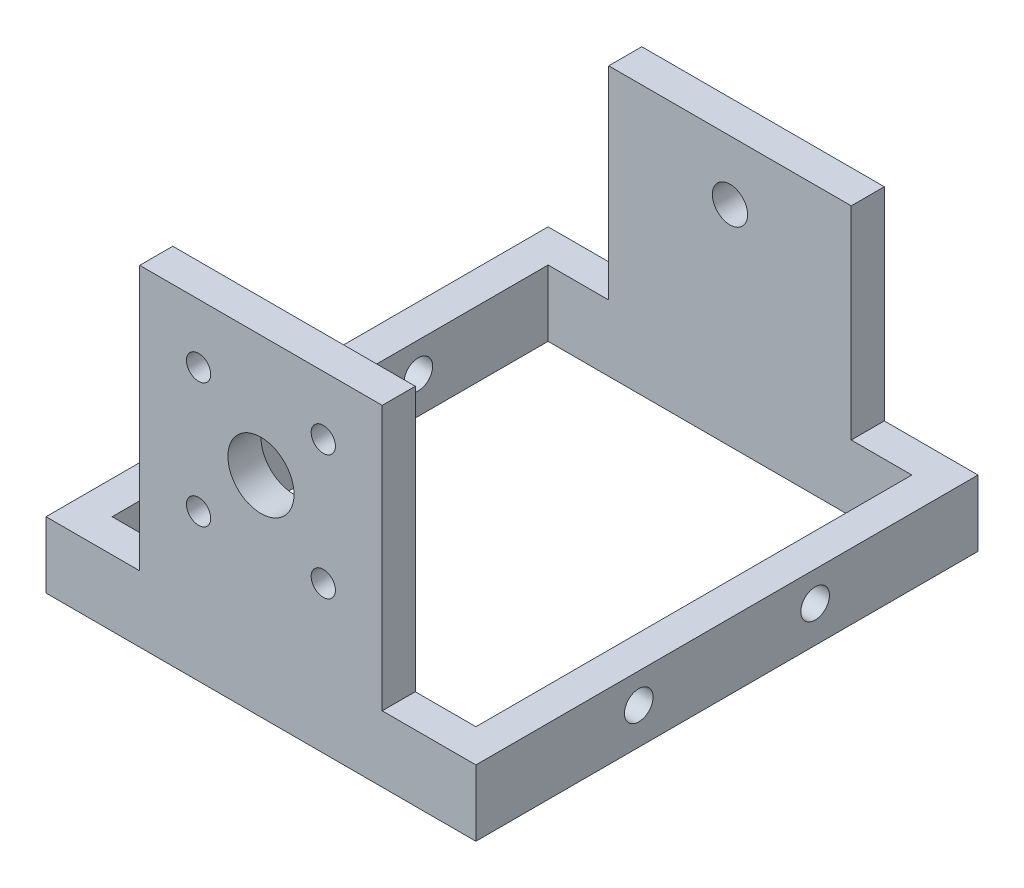
SolidWorks part; units mm, degrees
ref_plane "Front Plane" through (0, 0, 0) normal (0, 0, 1) x (1, 0, 0)
ref_plane "Top Plane" through (0, 0, 0) normal (0, 1, 0) x (1, 0, 0)
ref_plane "Right Plane" through (0, 0, 0) normal (1, 0, 0) x (0, 0, -1)
sketch "Sketch1" plane through (0, 0, 0) normal (0, 1, 0) x (1, 0, 0)
  line L0 (-55, 0) -> (55, 0) construction
  line L1 (19.5, 22.775) -> (-19.5, 22.775)
  line L2 (19.5, 22.775) -> (19.5, -22.775)
  line L3 (19.5, -22.775) -> (-19.5, -22.775)
  line L4 (-19.5, 22.775) -> (-19.5, -22.775)
  line L5 (19.5, 22.775) -> (-19.5, -22.775) construction
  line L6 (19.5, -22.775) -> (-19.5, 22.775) construction
  line L7 (16.5, 19.775) -> (-16.5, 19.775)
  line L8 (16.5, 19.775) -> (16.5, -19.775)
  line L9 (16.5, -19.775) -> (-16.5, -19.775)
  line L10 (-16.5, 19.775) -> (-16.5, -19.775)
  line L11 (16.5, 19.775) -> (-16.5, -19.775) construction
  line L12 (16.5, -19.775) -> (-16.5, 19.775) construction
  line L13 (-11, -19.775) -> (11, -19.775)
  line L14 (-11, -19.775) -> (-11, -22.775)
  line L15 (-11, -22.775) -> (11, -22.775)
  line L16 (11, -19.775) -> (11, -22.775)
  line L17 (-11, 22.775) -> (11, 22.775)
  line L18 (11, 19.775) -> (11, 22.775)
  line L19 (-11, 19.775) -> (11, 19.775)
  line L20 (-11, 19.775) -> (-11, 22.775)
  point P0 (0, 0)
  point P6 (0, 0)
  point P15 (0, -19.775)
  dimension "D1" = 33
  dimension "D2" = 3
  dimension "D3" = 3
  dimension "D4" = 39.55
  dimension "D5" = 22
extrude "Boss-Extrude1" add sketch "Sketch1" along normal blind 6 contours L7 L20 L1 L4 L3 L14 L9 L10 | L18 L7 L8 L9 L16 L3 L2 L1 region at (17.1733, 0, 0) region at (-17.1733, 0, 0)
extrude "Boss-Extrude2" add sketch "Sketch1<3>" along normal blind 30 contours L16 L9 L14 L3 region at (0, 0, 21.275)
sketch "Sketch1<3>" plane through (0, 0, 0) normal (0, 1, 0) x (1, 0, 0) same geometry as "Sketch1"
extrude "Boss-Extrude3" add sketch "Sketch1<4>" along normal blind 24.4 contours L20 L7 L18 L1 region at (0, 0, -21.275)
sketch "Sketch1<4>" plane through (0, 0, 0) normal (0, 1, 0) x (1, 0, 0) same geometry as "Sketch1"
sketch "Sketch3" plane through (-19.5, 0, 0) normal (-1, 0, 0) x (0, 0, 1)
  line L1 (0, -16.5) -> (0, 16.5) construction
  line L2 (21.45, 0) -> (-21.45, 0) construction
  circle A0 centre (-8, 3.3) radius 1.3
  circle A1 centre (8, 3.3) radius 1.3
  dimension "D1" = 2.6
  dimension "D2" = 8
  dimension "D3" = 3.3
extrude "Cut-Extrude1" cut sketch "Sketch3" against normal up to surface (39 mm away) up to face at (19.5, 3, 0)
sketch "Sketch4" plane through (0, 0, -22.775) normal (0, 0, -1) x (-1, 0, 0)
  line L0 (-11, 24.4) -> (11, 24.4) construction
  circle A0 centre (0, 19) radius 1.6
  point P4 (0, 24.4)
  dimension "D2" = 3.2
  dimension "D1" = 5.4
extrude "Cut-Extrude2" cut sketch "Sketch4" against normal up to surface (3 mm away) up to face at (0, 9.1, -19.775)
sketch "Sketch5" plane through (0, 0, 22.775) normal (0, 0, 1) x (1, 0, 0)
  line L0 (-11, 30) -> (11, 8) construction
  line L1 (11, 30) -> (11, 6) construction
  line L2 (11, 30) -> (-11, 8) construction
  line L3 (-11, 30) -> (-11, 6) construction
  circle A0 centre (0, 19) radius 3
  circle A1 centre (5.6569, 24.6569) radius 1.1
  dimension "D2" = 6
  dimension "D3" = 2.2
  dimension "D1" = 22
  dimension "D4" = 8
extrude "Cut-Extrude3" cut sketch "Sketch5" against normal up to surface (3 mm away) up to face at (0, 10.5, 19.775)
pattern_circular "CirPattern1" count 4 over 360 about axis through (0, 19, 22.775) along (0, 0, 1) of "Cut-Extrude3"
move or copy body "Body-Move/Copy1" [suppressed] bodies to move or copy 111
